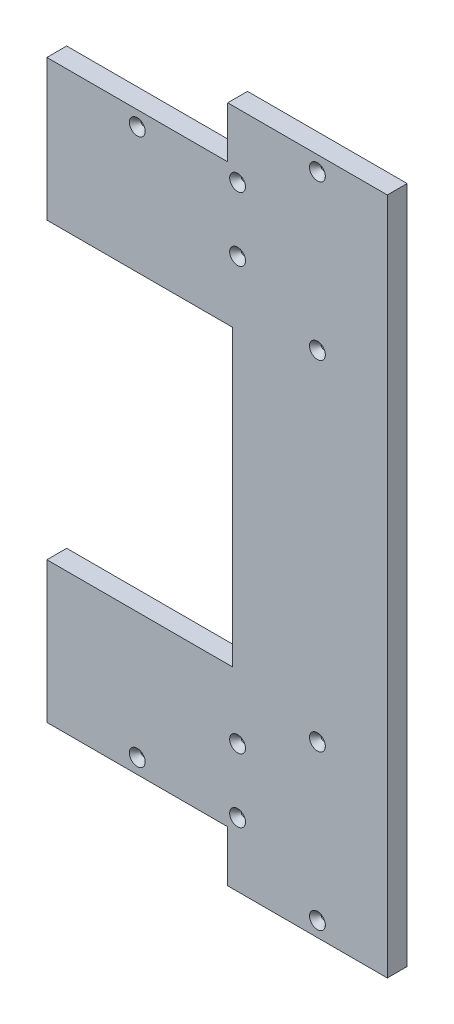
SolidWorks part; units mm, degrees
material "Beech"
ref_plane "Front Plane" through (0, 0, 0) normal (0, 0, 1) x (1, 0, 0)
ref_plane "Top Plane" through (0, 0, 0) normal (0, 1, 0) x (1, 0, 0)
ref_plane "Right Plane" through (0, 0, 0) normal (1, 0, 0) x (0, 0, -1)
sketch "Sketch1" plane through (0, 0, 0) normal (0, 0, 1) x (1, 0, 0)
  line L1 (-81.8518, 217.3) -> (161.737, 217.3)
  line L2 (-81.8518, 217.3) -> (-81.8518, -217.3)
  line L3 (-81.8518, -217.3) -> (161.737, -217.3)
  line L4 (161.737, 217.3) -> (161.737, -217.3)
  line L5 (72.1361, 217.3) -> (161.737, 217.3) construction
extrude "Boss-Extrude1" add sketch "Sketch1" along normal blind 12.7
sketch "Sketch2" plane through (0, 0, 0) normal (0, 0, -1) x (-1, 0, 0)
  line L1 (-59.4361, 184.525) -> (81.8518, 184.525)
  line L2 (-59.4361, 184.525) -> (-59.4361, 217.3)
  line L3 (-59.4361, 217.3) -> (81.8518, 217.3)
  line L4 (81.8518, 184.525) -> (81.8518, 217.3)
  line L5 (-59.4361, -184.525) -> (81.8518, -184.525)
  line L6 (-59.4361, -184.525) -> (-59.4361, -217.3)
  line L7 (-59.4361, -217.3) -> (81.8518, -217.3)
  line L8 (81.8518, -184.525) -> (81.8518, -217.3)
extrude "Cut-Extrude1" cut sketch "Sketch2" against normal up to next
sketch "Sketch3" plane through (0, 0, 12.7) normal (0, 0, 1) x (1, 0, 0)
  line L0 (-81.8518, 184.525) -> (-81.8518, -184.525) construction
  line L1 (59.4361, 91.075) -> (-81.8518, 91.075) construction
  line L2 (59.4361, 91.075) -> (59.4361, -91.075) construction
  line L3 (59.4361, -91.075) -> (-81.8518, -91.075) construction
  line L4 (-81.8518, 91.075) -> (-81.8518, -91.075) construction
  line L5 (-81.8518, 91.075) -> (59.4361, 91.075) construction
  line L6 (-81.8518, -91.075) -> (59.4361, -91.075) construction
  line L7 (59.4361, 165.475) -> (59.4361, -165.475) construction
  line L8 (62.6111, 94.25) -> (-56.4518, 94.25)
  line L9 (-85.0268, 94.25) -> (-85.0268, -94.25)
  line L10 (62.6111, -94.25) -> (-56.4518, -94.25)
  line L11 (62.6111, 94.25) -> (62.6111, -94.25)
  line L12 (-81.8518, 94.25) -> (-85.0268, 94.25)
  line L13 (-81.8518, 184.525) -> (-56.4518, 184.525)
  line L14 (-81.8518, 184.525) -> (-81.8518, 94.25)
  line L16 (-56.4518, 184.525) -> (-56.4518, 94.25)
  line L17 (62.6111, 94.25) -> (-85.0268, 94.25) construction
  line L18 (-81.8518, -94.25) -> (-85.0268, -94.25)
  line L19 (-81.8518, -184.525) -> (-56.4518, -184.525)
  line L20 (-81.8518, -184.525) -> (-81.8518, -94.25)
  line L22 (-56.4518, -184.525) -> (-56.4518, -94.25)
  line L23 (62.6111, -94.25) -> (-85.0268, -94.25) construction
  dimension "D2" = 25.4
  dimension "D1" = 3.175
extrude "Cut-Extrude2" cut sketch "Sketch3" against normal up to next
hole_wizard "Hole1" positions "Sketch4" profile "Sketch5" legacy
sketch "Sketch4" plane through (449.8285, 0, 12.7) normal (0, 0, 1) x (0, 1, 0)
  line L0 (207.775, 377.6924) -> (207.775, 288.0915) construction
  line L4 (108.65, 377.6924) -> (108.65, 288.0915) construction
  line L8 (175, 506.2803) -> (175, 390.3924) construction
  line L12 (94.25, 390.3924) -> (94.25, 377.6924) construction
  line L17 (94.25, 384.0424) -> (217.3, 384.0424) construction
  line L19 (94.25, 384.0424) -> (135.2667, 384.0424)
  line L20 (135.2667, 384.0424) -> (176.2833, 384.0424)
  line L21 (176.2833, 384.0424) -> (217.3, 384.0424)
  line L22 (0, 288.0915) -> (0, 390.3924) construction
  point P39 (108.65, 332.8919)
  point P41 (207.775, 332.8919)
  point P43 (175, 448.3363)
  point P47 (135.2667, 384.0424)
  point P49 (176.2833, 384.0424)
  point P65 (-175, 448.3363)
  point P66 (-135.2667, 384.0424)
  point P67 (-176.2833, 384.0424)
  point P68 (-207.775, 332.8919)
  point P69 (-108.65, 332.8919)
sketch "Sketch5" plane through (116.9365, -108.65, 12.7) normal (1, 0, 0) x (0, -1, 0)
  line L0 (0, 0) -> (0, 39.0539)
  line L1 (0, 39.0539) -> (1.5875, 38.1)
  line L2 (1.5875, 38.1) -> (1.5875, 4.0177)
  line L3 (1.5875, 4.0177) -> (5.08, 0)
  line L4 (5.08, 0) -> (0, 0)
  line L5 (0, -14.3089) -> (0, 102.4216) construction
  line L6 (0, 39.0539) -> (-1.5875, 38.1) construction
  line L7 (-1.5875, 4.0177) -> (-5.08, 0) construction
  dimension "Diameter" = 3.175
  dimension "Depth" = 38.1
  dimension "C-Sink Diameter" = 10.16
  dimension "C-Sink Angle" = 82
  dimension "Drill Angle" = 118
